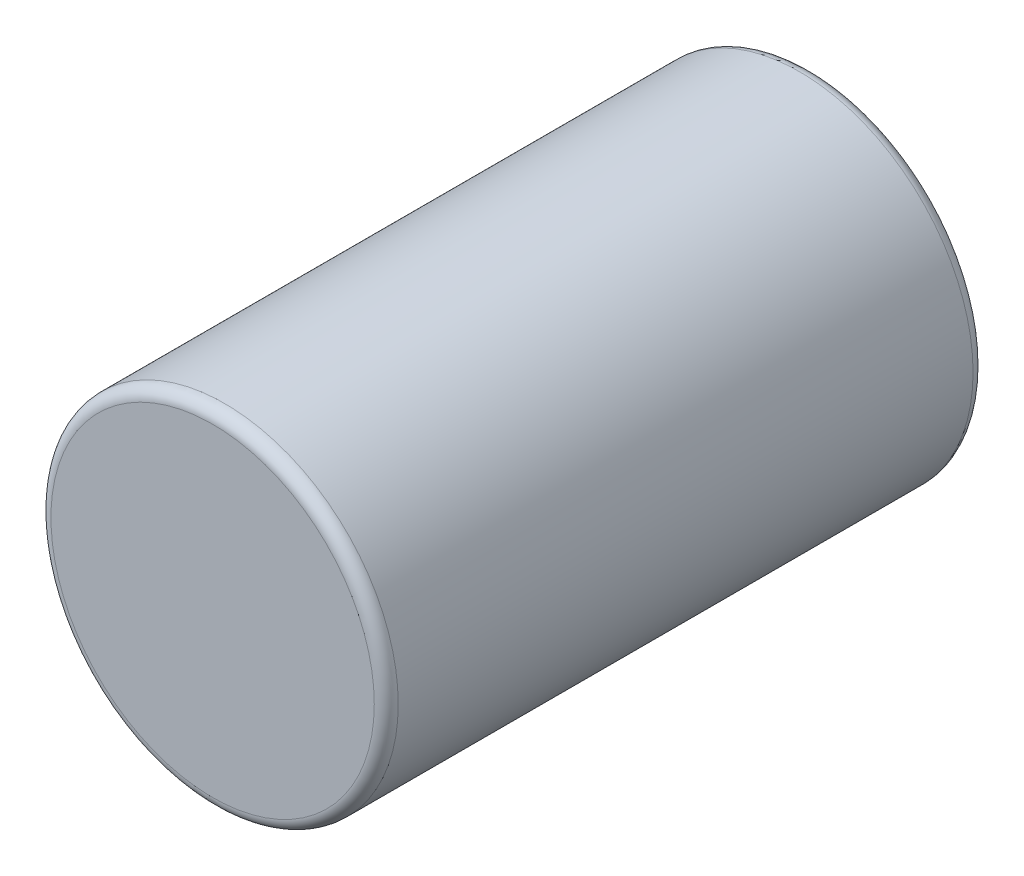
SolidWorks part; units mm, degrees
material "Aleación 1060"
ref_plane "Alzado" through (0, 0, 0) normal (0, 0, 1) x (1, 0, 0)
ref_plane "Planta" through (0, 0, 0) normal (0, 1, 0) x (1, 0, 0)
ref_plane "Vista lateral" through (0, 0, 0) normal (1, 0, 0) x (0, 0, -1)
sketch "Croquis1" plane through (0, 0, 0) normal (0, 0, 1) x (1, 0, 0)
  circle A0 centre (0, 0) radius 0.725
  dimension "D1" = 1.45
extrude "Saliente-Extruir1" add sketch "Croquis1" along normal blind 2.5
fillet "Redondeo1" radius 0.05 2 edges at (0.725, 0, 0) (0.725, 0, 2.5)
